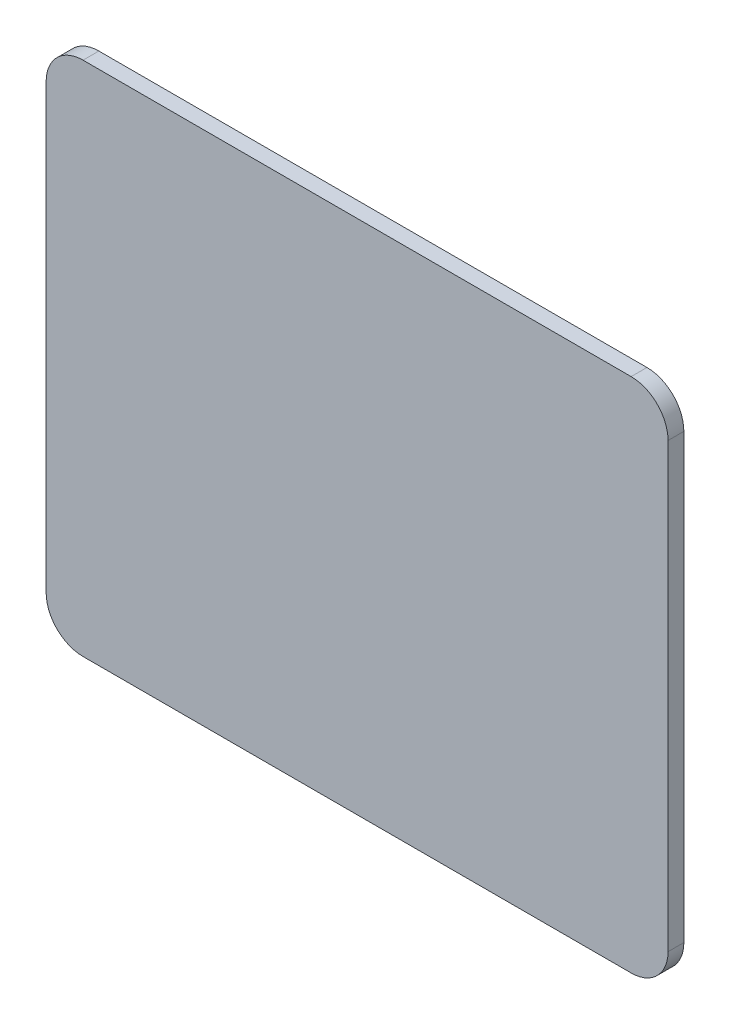
SolidWorks part; units mm, degrees
ref_plane "Front Plane" through (0, 0, 0) normal (0, 0, 1) x (1, 0, 0)
ref_plane "Top Plane" through (0, 0, 0) normal (0, 1, 0) x (1, 0, 0)
ref_plane "Right Plane" through (0, 0, 0) normal (1, 0, 0) x (0, 0, -1)
sketch "Sketch1" plane through (0, 0, 0) normal (0, 0, 1) x (1, 0, 0)
  line L4 (-72.1221, 155) -> (-72.1221, 71) construction
  line L5 (-64.1221, 63) -> (39.8779, 63) construction
  line L6 (39.8779, 163) -> (-64.1221, 163) construction
  line L7 (47.8779, 71) -> (47.8779, 155) construction
  line L8 (-71.1221, 155) -> (-71.1221, 71)
  line L9 (-64.1221, 64) -> (39.8779, 64)
  line L10 (46.8779, 71) -> (46.8779, 155)
  line L11 (39.8779, 162) -> (-64.1221, 162)
  arc A4 (-64.1221, 163) -> (-72.1221, 155) centre (-64.1221, 155) ccw construction
  arc A5 (-72.1221, 71) -> (-64.1221, 63) centre (-64.1221, 71) ccw construction
  arc A6 (39.8779, 63) -> (47.8779, 71) centre (39.8779, 71) ccw construction
  arc A7 (47.8779, 155) -> (39.8779, 163) centre (39.8779, 155) ccw construction
  arc A8 (-71.1221, 71) -> (-64.1221, 64) centre (-64.1221, 71) ccw
  arc A9 (39.8779, 64) -> (46.8779, 71) centre (39.8779, 71) ccw
  arc A10 (46.8779, 155) -> (39.8779, 162) centre (39.8779, 155) ccw
  arc A11 (-64.1221, 162) -> (-71.1221, 155) centre (-64.1221, 155) ccw
  dimension "D1" = 1
extrude "Boss-Extrude1" add sketch "Sketch1" against normal blind 3
